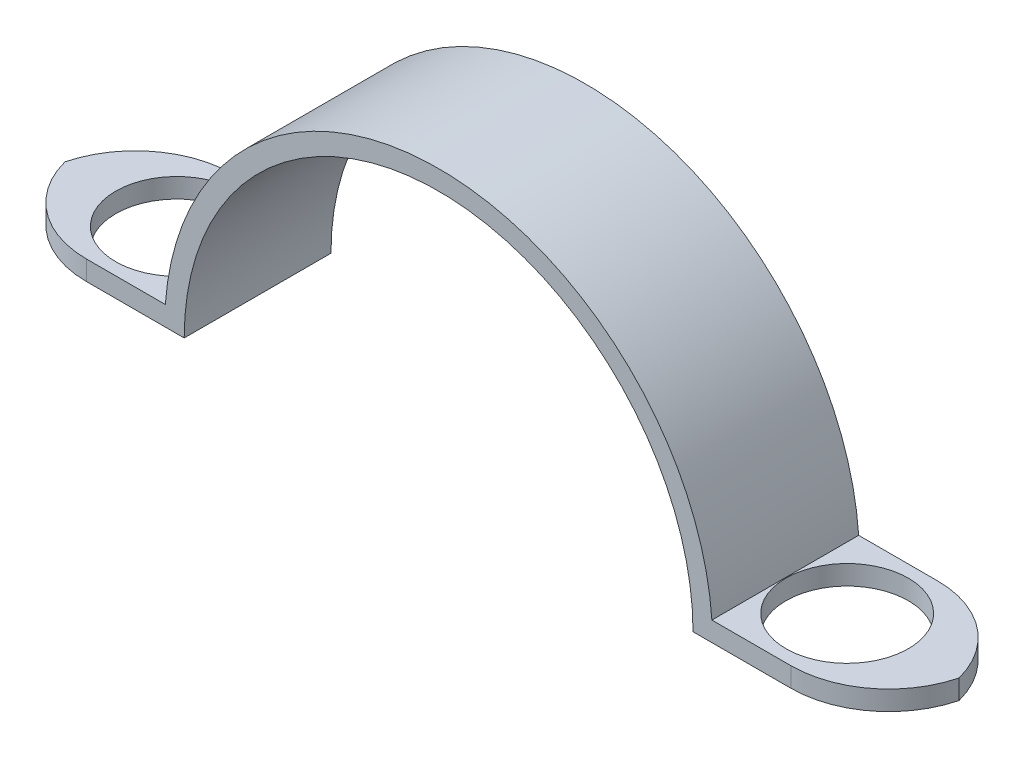
SolidWorks part; units mm, degrees
ref_plane "Front Plane" through (0, 0, 0) normal (0, 0, 1) x (1, 0, 0)
ref_plane "Top Plane" through (0, 0, 0) normal (0, 1, 0) x (1, 0, 0)
ref_plane "Right Plane" through (0, 0, 0) normal (1, 0, 0) x (0, 0, -1)
sketch "Sketch1" plane through (0, 0, 0) normal (0, 0, 1) x (1, 0, 0)
  line L0 (-37.8084, 0) -> (30.1006, 0) construction
  line L1 (-26, 0) -> (-46, 0)
  line L2 (26, 0) -> (46, 0)
  arc A1 (26, 0) -> (-26, 0) centre (0, 0) ccw
  dimension "D1" = 52
  dimension "D2" = 20
  dimension "D3" = 20
extrude "Extrude-Thin2" add sketch "Sketch1" against normal blind 15 thin thin type one direction reverse wall 2
sketch "Sketch6" plane through (0, 2, 0) normal (0, 1, 0) x (1, 0, 0)
  line L0 (-46, 15) -> (-46, 0) construction
  line L1 (-46, 15) -> (-27.9285, 15) construction
  circle A0 centre (-34.25, 7.5) radius 6.25
  circle A1 centre (34.25, 7.5) radius 6.25
  dimension "D1" = 12.5
  dimension "D2" = 68.5
  dimension "D3" = 11.75
  dimension "D4" = 7.5
extrude "Cut-Extrude1" cut sketch "Sketch6" against normal through all
fillet "Fillet1" radius 10 4 edges at (-46, 1, -15) (-46, 1, 0) (46, 1, -15) (46, 1, 0)
